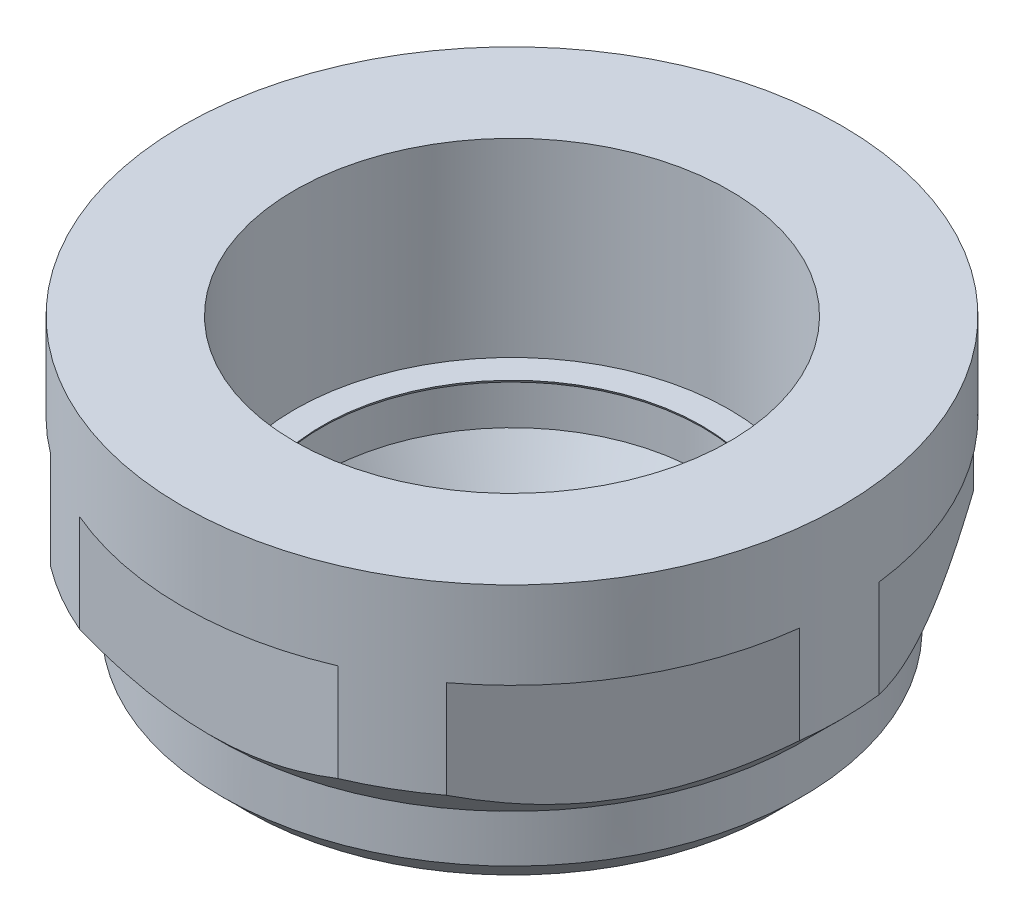
SolidWorks part; units mm, degrees
material "Cast Alloy Steel"
ref_plane "Front Plane" through (0, 0, 0) normal (0, 0, 1) x (1, 0, 0)
ref_plane "Top Plane" through (0, 0, 0) normal (0, 1, 0) x (1, 0, 0)
ref_plane "Right Plane" through (0, 0, 0) normal (1, 0, 0) x (0, 0, -1)
sketch "Sketch0" plane through (0, 0, 0) normal (0, 0, 1) x (1, 0, 0)
  line L0 (0, 0) -> (0, 45.1577) construction
  line L1 (0, 0) -> (37.9868, 0) construction
  line L2 (-12.5, 11.3) -> (-12.5, 4.3)
  line L3 (-12.5, 4.3) -> (-11, 2.8)
  line L4 (-11, 2.8) -> (-11, 1)
  line L5 (-11, 1) -> (-10, 0)
  line L6 (-10, 0) -> (0, 0)
  line L7 (-12.5, 11.3) -> (0, 11.3)
  line L8 (0, 11.3) -> (0, 0)
  dimension "D1" = 11.3
  dimension "D2" = 25
  dimension "D3" = 1
  dimension "D4" = 45
  dimension "D5" = 7
  dimension "D6" = 22
revolve "Rotation1" add sketch "Sketch0" angle 360 about L0
ref_axis "Axis1" through (0, 11.3, 0) along (0, -1, 0)
sketch "Sketch1" plane through (0, 0, 0) normal (1, 0, 0) x (0, 0, -1)
  line L0 (0, 0) -> (0, 12.2039) construction
  line L1 (-5.8066, 0) -> (-7.25, 2.5)
  line L2 (-10, 0) -> (10, 0) construction
  line L3 (-7.25, 2.5) -> (-7.25, 4)
  line L4 (-7.25, 4) -> (-7.1923, 4.1)
  line L6 (-7.1923, 4.1) -> (0, 4.1)
  line L7 (0, 4.1) -> (0, 0)
  line L8 (0, 0) -> (-5.8066, 0)
  dimension "D1" = 30
  dimension "D2" = 14.5
  dimension "D3" = 2.5
  dimension "D4" = 4.1
  dimension "D5" = 30
  dimension "D6" = 4
revolve "Revolved Cut1" cut sketch "Sketch1" angle 360 about L0
hole_wizard "Hole/Thread" positions "Sketch2" profile "Sketch3" tap size "M18x1.5" standard "ISO" end condition up to next
sketch "Sketch2" plane through (0, 11.3, 0) normal (0, 1, 0) x (-1, 0, 0)
  point P0 (0, 0)
cosmetic thread "Bore thread 1" parameters "D2"=18
sketch "Sketch3" plane through (0, 11.3, 0) normal (1, 0, 0) x (0, 0, 1)
  line L0 (0, 0) -> (0, 7.2)
  line L1 (0, 7.2) -> (8.25, 7.2)
  line L2 (8.25, 7.2) -> (8.25, 0)
  line L5 (8.25, 0) -> (0, 0)
  line L11 (0, -6.35) -> (0, 107.95) construction
  dimension "Bohrerdurchmesser" = 16.5
  dimension "Bohrungstiefe" = 7.2
sketch "Sketch5" plane through (0, 0, 0) normal (0, -1, 0) x (1, 0, 0)
  line L0 (0, 0) -> (0, 10.7506) construction
  line L1 (0, 0) -> (10.9929, 0) construction
  line L3 (-7, 12.5) -> (7, 12.5)
  line L4 (-7, 12.5) -> (-7, 11.5)
  line L5 (-7, 11.5) -> (7, 11.5)
  line L6 (7, 12.5) -> (7, 11.5)
  circle A0 centre (0, 0) radius 12.5 construction
  dimension "D1" = 23
  dimension "D2" = 7
  dimension "D3" = 7
extrude "Extrude Cut" cut sketch "Sketch5" against normal blind 8
pattern_circular "Circular Pattern" count 6 over 360 about axis through (0, 11.3, 0) along (0, -1, 0) of "Extrude Cut"
